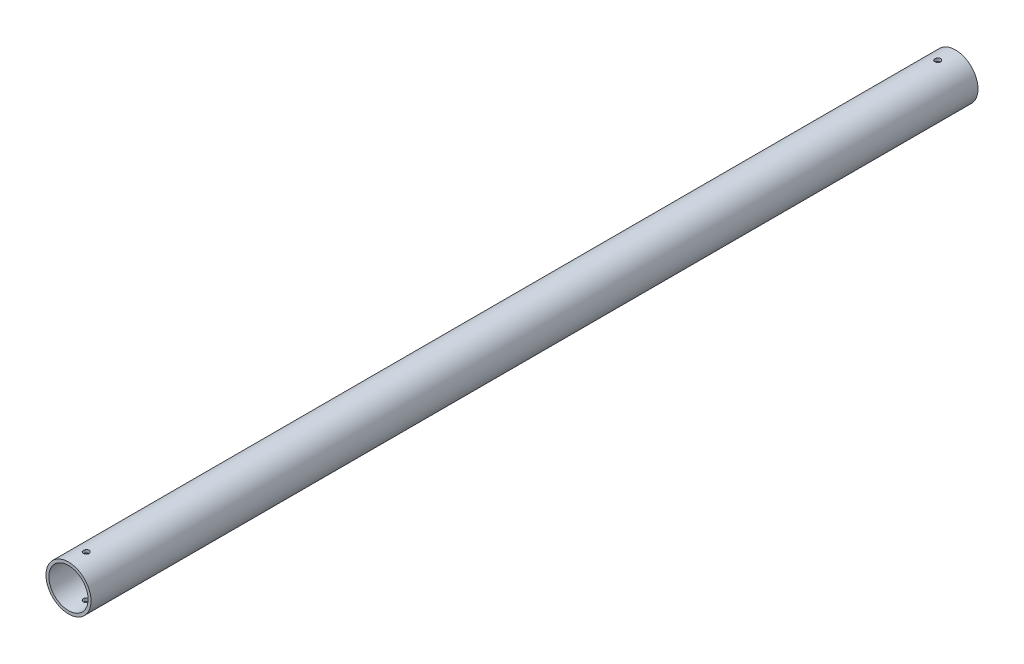
SolidWorks part; units mm, degrees
material "6063-T6, Rod (SS)"
ref_plane "Front Plane" through (0, 0, 0) normal (0, 0, 1) x (1, 0, 0)
ref_plane "Top Plane" through (0, 0, 0) normal (0, 1, 0) x (1, 0, 0)
ref_plane "Right Plane" through (0, 0, 0) normal (1, 0, 0) x (0, 0, -1)
sketch "Sketch1" plane through (0, 0, 0) normal (0, 0, 1) x (1, 0, 0)
  circle A0 centre (0, 0) radius 12.7
  circle A1 centre (0, 0) radius 11.049
  dimension "D1" = 25.4
  dimension "D2" = 22.098
extrude "Boss-Extrude1" add sketch "Sketch1" along normal mid plane 500
sketch "Sketch2" plane through (0, 0, 0) normal (0, 1, 0) x (1, 0, 0)
  line L0 (-12.7, -250) -> (12.7, -250) construction
  line L1 (-12.7, -240) -> (12.7, -240) construction
  line L2 (-12.7, 250) -> (-12.7, -250) construction
  line L3 (12.7, -250) -> (12.7, 250) construction
  circle A0 centre (0, -240) radius 1.6
  dimension "D1" = 3.2
  dimension "D2" = 10
extrude "Cut-Extrude1" cut sketch "Sketch2" against normal through all both and the other way through all
mirror "Mirror1" about plane through (0, 0, 0) normal (0, 0, 1) of "Cut-Extrude1"
